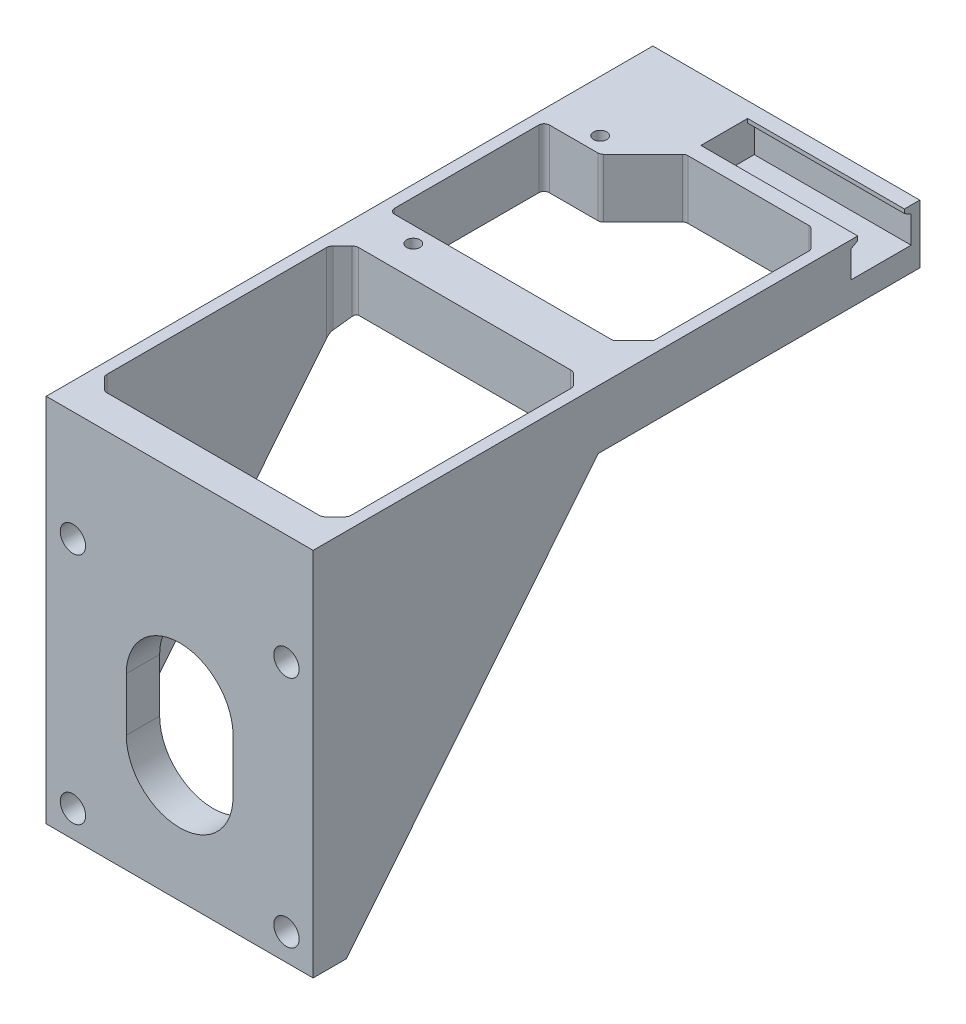
SolidWorks part; units mm, degrees
ref_plane "Front Plane" through (0, 0, 0) normal (0, 0, 1) x (1, 0, 0)
ref_plane "Top Plane" through (0, 0, 0) normal (0, 1, 0) x (1, 0, 0)
ref_plane "Right Plane" through (0, 0, 0) normal (1, 0, 0) x (0, 0, -1)
sketch "Sketch1" plane through (0, 0, 0) normal (0, 1, 0) x (1, 0, 0)
  line L0 (0, 0) -> (0, 59.6401) construction
  line L1 (-20, -19.2885) -> (-21.7, -19.2885)
  line L2 (20, 17.7115) -> (21.7, 17.7115)
  line L3 (20, 17.7115) -> (20, 69.9115)
  line L4 (20, 69.9115) -> (21.7, 69.9115)
  line L5 (21.7, 17.7115) -> (21.7, 69.9115)
  line L6 (20, 17.7115) -> (21.7, 17.7115)
  line L7 (20, 17.7115) -> (20, -19.2885)
  line L8 (20, -19.2885) -> (21.7, -19.2885)
  line L9 (21.7, 17.7115) -> (21.7, -19.2885)
  line L10 (-21.7, 17.7115) -> (-21.7, -19.2885)
  line L11 (-20, 17.7115) -> (-21.7, 17.7115)
  line L12 (-20, 17.7115) -> (-20, -19.2885)
  line L13 (-20, 69.9115) -> (-21.7, 69.9115)
  line L14 (-21.7, 17.7115) -> (-21.7, 69.9115)
  line L15 (-20, 17.7115) -> (-21.7, 17.7115)
  line L16 (-20, 17.7115) -> (-20, 69.9115)
  dimension "18" = 20
  dimension "D2" = 1.7
  dimension "D3" = 37
  dimension "D4" = 52.2
extrude "Boss-Extrude1" add sketch "Sketch1" against normal blind 8.8 from offset 1 contours L12 L11 L10 L1 | L11 L16 L13 L14 | L3 L2 L5 L4 offset against normal yes
sketch "Sketch4" plane through (0, -9.8, 0) normal (0, -1, 0) x (1, 0, 0)
  line L0 (-21.7, -69.9115) -> (-21.7, 19.2885) construction
  line L1 (18.3, -69.9115) -> (-21.7, -69.9115)
  line L2 (18.3, -69.9115) -> (18.3, -58.3115)
  line L3 (18.3, -58.3115) -> (-21.7, -58.3115)
  line L4 (-21.7, -69.9115) -> (-21.7, -58.3115)
  line L13 (-20, -69.9115) -> (-21.7, -69.9115) construction
  dimension "D1" = 11.6
  dimension "D2" = 40
extrude "Boss-Extrude3" add sketch "Sketch4" against normal up to surface (8.8 mm away)
sketch "Sketch3" plane through (0, -9.8, 0) normal (0, -1, 0) x (1, 0, 0)
  line L0 (-21.7, -69.9115) -> (-21.7, 19.2885) construction
  line L1 (-21.7, -58.9115) -> (-7.7, -58.9115)
  line L2 (-21.7, -58.9115) -> (-21.7, -51.9115)
  line L3 (-21.7, -51.9115) -> (-7.7, -51.9115)
  line L4 (-7.7, -58.9115) -> (-7.7, -51.9115)
  line L6 (0, 0) -> (0, -31.4212) construction
  line L13 (18.3, -69.9115) -> (-21.7, -69.9115) construction
  line L14 (-21.7, -40.3115) -> (-3.8096, -40.3115) construction
  line L15 (-21.7, -28.7115) -> (-7.7, -28.7115)
  line L16 (-7.7, -21.7115) -> (-7.7, -28.7115)
  line L17 (-21.7, -21.7115) -> (-7.7, -21.7115)
  line L18 (-21.7, -21.7115) -> (-21.7, -28.7115)
  line L19 (-20, -58.3115) -> (-20, 19.2885) construction
  circle A0 centre (-14, -54.3115) radius 1
  circle A2 centre (-14, -26.3115) radius 1
  dimension "D4" = 2.4
  dimension "D5" = 2
  dimension "D1" = 14
  dimension "D2" = 15.6
  dimension "D3" = 7
  dimension "D6" = 6
  dimension "D7" = 14
extrude "Servo Holder" add sketch "Sketch3" along normal blind 1 and the other way offset from surface (8.8 mm away) 1 other way up to plane "Top Plane"
sketch "Sketch37" plane through (0, -1, 0) normal (0, 1, 0) x (1, 0, 0)
  line L0 (-7.7, 21.7115) -> (-20, 21.7115) construction
  line L1 (18.3, 21.7115) -> (-7.7, 21.7115)
  line L2 (18.3, 21.7115) -> (18.3, 28.7115)
  line L3 (18.3, 28.7115) -> (-7.7, 28.7115)
  line L4 (-7.7, 21.7115) -> (-7.7, 28.7115)
  line L5 (-21.7, 69.9115) -> (-21.7, -19.2885) construction
  dimension "D1" = 40
extrude "Boss-Extrude19" add sketch "Sketch37" against normal up to surface (9.8 mm away) up to face at (-14.7, -10.8, -25.2115)
sketch "Sketch29" plane through (0, 0, -69.9115) normal (0, 0, -1) x (-1, 0, 0)
  line L1 (21.7, -9.8) -> (-27.4015, -9.8)
  line L2 (21.7, -9.8) -> (21.7, -16.1774)
  line L3 (21.7, -16.1774) -> (-27.4015, -16.1774)
  line L4 (-27.4015, -9.8) -> (-27.4015, -16.1774)
extrude "Cut-Extrude10" cut sketch "Sketch29" against normal through all both and the other way through all
sketch "Sketch35" plane through (18.3, 0, 0) normal (1, 0, 0) x (0, 0, -1)
  line L0 (-2, -1) -> (21.7115, -1)
  line L1 (21.7115, -1) -> (21.7115, -9.8)
  line L4 (-19.2885, -1) -> (-2, -1)
  line L5 (21.7115, -9.8) -> (21.7115, -1) construction
  line L6 (-19.2885, -9.8) -> (-19.2885, -1) construction
  line L9 (21.7115, -1) -> (28.7115, -1) construction
  line L11 (21.7115, -9.8) -> (-19.2885, -9.8)
  line L12 (-19.2885, -9.8) -> (-19.2885, -1)
  line L13 (69.9115, -9.8) -> (-19.2885, -9.8) construction
extrude "Boss-Extrude17" add sketch "Sketch35" against normal blind 3
sketch "Sketch39" plane through (0, -1, 0) normal (0, 1, 0) x (1, 0, 0)
  line L0 (-21.7, 69.9115) -> (18.3, 69.9115) construction
  line L1 (18.3, 28.7115) -> (16.6, 28.7115)
  line L2 (18.3, 28.7115) -> (18.3, 69.9115)
  line L3 (18.3, 69.9115) -> (16.6, 69.9115)
  line L4 (16.6, 28.7115) -> (16.6, 69.9115)
  line L5 (-20, 28.7115) -> (18.3, 28.7115) construction
  line L6 (18.3, -19.2885) -> (18.3, 28.7115) construction
  point P7 (18.3, 49.3115)
  dimension "D1" = 1.7
extrude "Boss-Extrude20" add sketch "Sketch39" against normal up to surface (8.8 mm away) up to face at (-2.5, -9.8, -27.4258)
sketch "Sketch40" plane through (18.3, 0, 0) normal (1, 0, 0) x (0, 0, -1)
  line L0 (-19.2885, -1) -> (69.9115, -1) construction
  line L1 (60.6115, -1) -> (67.6115, -1)
  line L2 (69.9115, -1) -> (69.9115, -9.8) construction
  line L6 (60.6115, -2.2) -> (59.6115, -2.2)
  line L7 (59.6115, -2.2) -> (59.6115, -6.2)
  line L8 (59.6115, -6.2) -> (68.6115, -6.2)
  line L9 (64.1115, -6.2) -> (64.1115, -1)
  line L13 (67.6115, -1) -> (67.6115, -2.2)
  line L15 (60.6115, -2.2) -> (60.6115, -1)
  line L17 (68.6115, -2.2) -> (68.6115, -6.2)
  line L18 (67.6115, -2.2) -> (68.6115, -2.2)
  point P9 (59.6115, -4.2)
  dimension "D1" = 5.8
  dimension "D2" = 3.5
  dimension "D3" = 4.5
  dimension "D4" = 4
  dimension "D5" = 1.2
  dimension "D6" = 3.5
extrude "Cut-Extrude13" cut sketch "Sketch40" against normal offset from surface (23.5 mm away) 16.5
chamfer "Chamfer2" distance 0.6 angle 60 2 edges at (6.55, -2.2, -60.6115) (6.55, -2.2, -67.6115)
chamfer "Chamfer3" distance 3 angle 45 2 edges at (16.6, -5.4, -28.7115) (16.6, -5.4, -58.3115)
chamfer "Chamfer4" distance 2.5 angle 45 1 edges at (-7.7, -5.4, -58.3115)
sketch "Sketch43" plane through (0, -1, 0) normal (0, 1, 0) x (1, 0, 0)
  line L0 (-5.2, 58.3115) -> (-11.6, 51.9115)
  line L1 (-7.7, 51.9115) -> (-20, 51.9115) construction
  line L2 (-11.6, 51.9115) -> (-5.2, 51.9115)
  line L3 (-5.2, 51.9115) -> (-5.2, 58.3115)
extrude "Cut-Extrude16" cut sketch "Sketch43" against normal blind 10
fillet "Fillet11" radius 0.8 8 edges at (-20, -5.4, -51.9115) (-20, -5.4, -28.7115) (13.6, -5.4, -28.7115) (16.6, -5.4, -31.7115) (16.6, -5.4, -55.3115) (13.6, -5.4, -58.3115) (-11.6, -5.4, -51.9115) (-5.2, -5.4, -58.3115)
sketch "Sketch51" plane through (0, -1, 0) normal (0, 1, 0) x (1, 0, 0)
  line L0 (18.3, -19.2885) -> (18.3, 60.6115) construction
  line L1 (-21.7, -19.2885) -> (18.3, -19.2885)
  line L2 (-21.7, -19.2885) -> (-21.7, 21.7115)
  line L3 (-21.7, 21.7115) -> (18.3, 21.7115)
  line L4 (18.3, -19.2885) -> (18.3, 21.7115)
extrude "Cut-Extrude17" cut sketch "Sketch51" against normal blind 10
ref_plane "Plane1" through (0, 0, 16) normal (0, 0, 1) x (1, 0, 0)
sketch "Sketch50" plane through (0, 0, 16) normal (0, 0, 1) x (1, 0, 0)
  line L0 (-1.7, -5) -> (-1.7, -71.7325) construction
  line L1 (-21.7, -35) -> (18.3, -35) construction
  line L2 (-21.7, -1) -> (18.3, -1)
  line L3 (-21.7, -1) -> (-21.7, -56.5)
  line L4 (-21.7, -56.5) -> (18.3, -56.5)
  line L5 (18.3, -1) -> (18.3, -56.5)
  line L6 (-1.7, -31) -> (-1.7, -39) construction
  line L7 (6.3, -31) -> (6.3, -39)
  line L8 (-9.7, -31) -> (-9.7, -39)
  line L9 (18.3, -9.8) -> (18.3, -1) construction
  line L14 (18.3, -1) -> (-21.7, -1) construction
  circle A0 centre (-17.7, -17.5) radius 1.9
  circle A1 centre (14.3, -17.5) radius 1.9
  circle A2 centre (14.3, -52.5) radius 1.9
  circle A3 centre (-17.7, -52.5) radius 1.9
  arc A4 (6.3, -31) -> (-9.7, -31) centre (-1.7, -31) ccw
  arc A5 (-9.7, -39) -> (6.3, -39) centre (-1.7, -39) ccw
  point P20 (-1.7, -35)
  dimension "D3" = 3.8
  dimension "D6" = 34
  dimension "D1" = 16
  dimension "D2" = 17.5
  dimension "D4" = 4
  dimension "D5" = 8
  dimension "D7" = 4
  dimension "D8" = 20
extrude "Boss-Extrude24" add sketch "Sketch50" along normal blind 5 separate body
sketch "Sketch53" plane through (0, -1, 0) normal (0, 1, 0) x (1, 0, 0)
  line L0 (-1.7, -16) -> (-1.7, 21.7115) construction
  line L1 (18.3, -16) -> (-21.7, -16) construction
  line L2 (18.3, 21.7115) -> (-21.7, 21.7115) construction
  line L3 (18.3, -16) -> (18.3, 21.7115)
  line L4 (18.3, 21.7115) -> (16.6, 21.7115)
  line L5 (16.6, 21.7115) -> (16.6, -16)
  line L6 (16.6, -16) -> (18.3, -16)
  line L7 (-20, 21.7115) -> (-20, -16)
  line L8 (-21.7, 21.7115) -> (-20, 21.7115)
  line L9 (-21.7, -16) -> (-21.7, 21.7115)
  line L10 (-20, -16) -> (-21.7, -16)
  dimension "D1" = 1.7
extrude "Boss-Extrude25" add sketch "Sketch53" against normal up to surface (8.8 mm away) up to face at (0.4978, -9.8, -45.6115)
chamfer "Chamfer6" distance 46.7 angle 38.92 2 edges at (17.45, -9.8, 16) (-20.85, -9.8, 16)
chamfer "Chamfer5" distance 2 angle 45 4 edges at (16.6, -5.4, -21.7115) (16.6, -28.75, 16) (-20, -28.75, 16) (-20, -5.4, -21.7115)
fillet "Fillet13" radius 1 12 edges at (16.6, -27.5116, 14) (14.6, -8.3119, 16) (16.6, -6.6369, -19.7115) (14.6, -5.4, -21.7115) (-18, -5.4, -21.7115) (-20, -6.6369, -19.7115) (-18, -8.3119, 16) (-20, -27.5116, 14) (-18, -55.4381, 16) (-18, -35, 16) (14.6, -55.4381, 16) (14.6, -35, 16)
